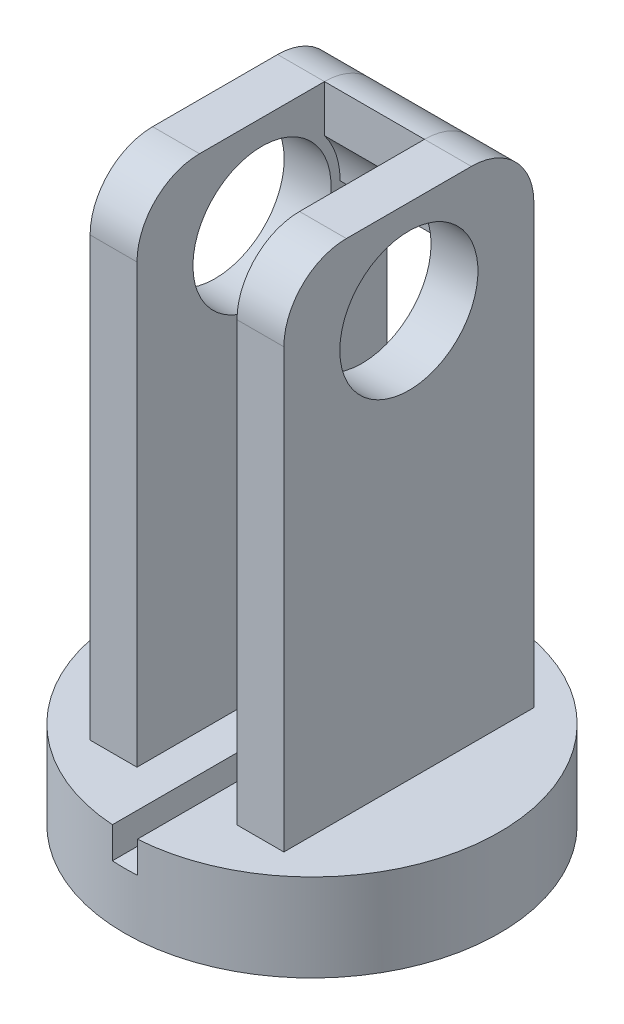
SolidWorks part; units mm, degrees
ref_plane "Front Plane" through (0, 0, 0) normal (0, 0, 1) x (1, 0, 0)
ref_plane "Top Plane" through (0, 0, 0) normal (0, 1, 0) x (1, 0, 0)
ref_plane "Right Plane" through (0, 0, 0) normal (1, 0, 0) x (0, 0, -1)
sketch "Sketch1" plane through (0, 0, 0) normal (0, 1, 0) x (1, 0, 0)
  circle A0 centre (0, 0) radius 30
  dimension "D1" = 60
extrude "Boss-Extrude1" add sketch "Sketch1" along normal blind 14
sketch "Sketch2" plane through (0, 0, 0) normal (0, -1, 0) x (1, 0, 0)
  circle A0 centre (0, 0) radius 11.05
  dimension "D1" = 22.1
extrude "Cut-Extrude1" cut sketch "Sketch2" against normal blind 7
sketch "Sketch5" plane through (0, 14, 0) normal (0, 1, 0) x (1, 0, 0)
  line L0 (0, 0) -> (-8, 0) construction
  line L1 (0, 0) -> (8, 0) construction
  line L2 (-8, -20) -> (-8, 20)
  line L3 (-8, 20) -> (-15.5, 20)
  line L4 (-15.5, 20) -> (-15.5, -20)
  line L5 (-15.5, -20) -> (-8, -20)
  line L7 (15.5, -20) -> (15.5, 20)
  line L8 (15.5, 20) -> (8, 20)
  line L9 (8, 20) -> (8, -20)
  line L10 (8, -20) -> (15.5, -20)
  dimension "D1" = 8
  dimension "D2" = 8
  dimension "D3" = 7.5
  dimension "D4" = 20
  dimension "D5" = 20
  dimension "D6" = 0
  dimension "D7" = 7.5
  dimension "D8" = 20
  dimension "D9" = 20
extrude "Boss-Extrude2" add sketch "Sketch5" along normal blind 80
sketch "Sketch7" plane through (-15.5, 0, 0) normal (-1, 0, 0) x (0, 0, 1)
  line L0 (20, 94) -> (20, 14) construction
  line L1 (-20, 94) -> (20, 94) construction
  circle A0 centre (0, 79) radius 11.05
  dimension "D1" = 20
  dimension "D3" = 22.1
  dimension "D2" = 15
fillet "Fillet1" radius 10 4 edges at (-11.75, 94, -20) (11.75, 94, -20) (11.75, 94, 20) (-11.75, 94, 20)
extrude "Cut-Extrude3" cut sketch "Sketch7" against normal through all and the other way through all
sketch "Sketch8" plane through (0, 14, 0) normal (0, 1, 0) x (1, 0, 0)
  line L0 (0, 0) -> (2, 0) construction
  line L1 (0, 0) -> (-2, 0) construction
  line L2 (2, 29.9333) -> (2, -29.9333)
  line L3 (-2, 29.9333) -> (-2, -29.9333)
  circle A0 centre (0, 0) radius 30 construction
  arc A1 (-2, -29.9333) -> (2, -29.9333) centre (0, 0) ccw
  arc A2 (2, 29.9333) -> (-2, 29.9333) centre (0, 0) ccw
  dimension "D1" = 2
  dimension "D2" = 2
extrude "Cut-Extrude4" cut sketch "Sketch8" against normal blind 5
sketch "Sketch9" plane through (8, 0, 0) normal (-1, 0, 0) x (0, 0, 1)
  line L0 (0, 79) -> (-10, 79) construction
  line L1 (-10, 86.5) -> (-10, 94)
  line L3 (-12.5, 79) -> (-20, 79)
  line L5 (-20, 84) -> (-20, 14) construction
  line L6 (-20, 79) -> (-20, 94)
  line L7 (-20, 94) -> (-10, 94)
  arc A3 (-10, 86.5) -> (-12.5, 79) centre (0, 79) ccw
  dimension "D1" = 12.5
extrude "Boss-Extrude4" add sketch "Sketch9" along normal up to surface (16 mm away) contours L7 L1 A3 L3 L6 up to face at (-8, 79, 11.05)
fillet "Fillet2" radius 10 1 edges at (0, 94, -20)
